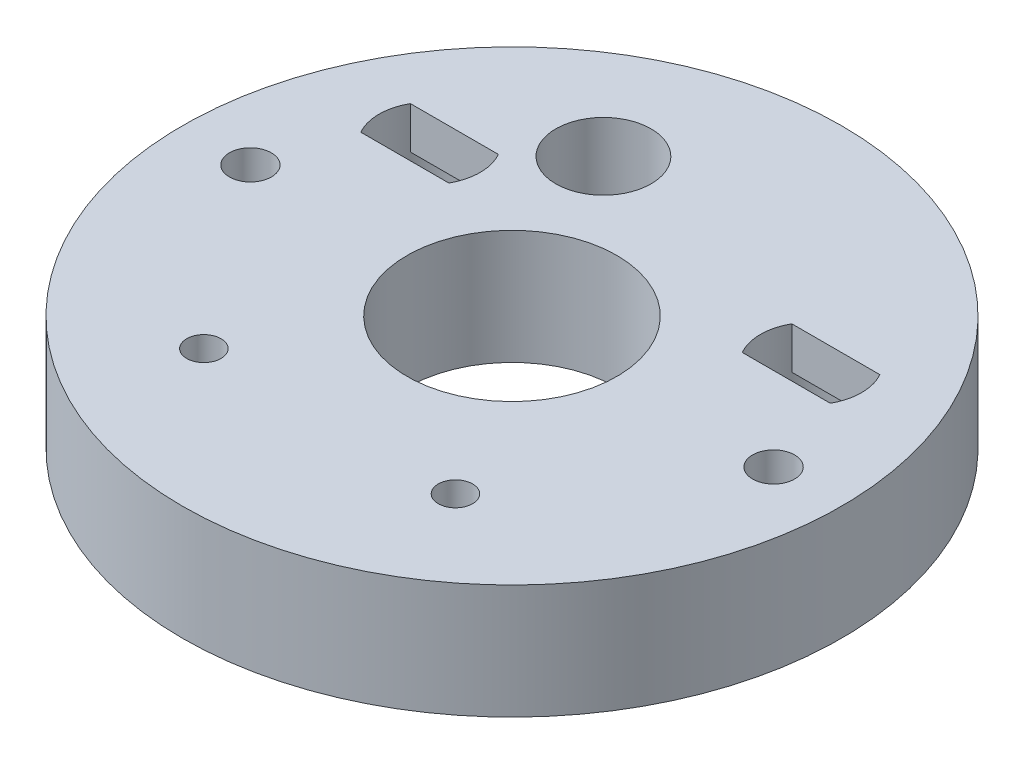
SolidWorks part; units mm, degrees
ref_plane "前视基准面" through (0, 0, 0) normal (0, 0, 1) x (1, 0, 0)
ref_plane "上视基准面" through (0, 0, 0) normal (0, 1, 0) x (1, 0, 0)
ref_plane "右视基准面" through (0, 0, 0) normal (1, 0, 0) x (0, 0, -1)
sketch "草图1" plane through (0, 0, 0) normal (0, 1, 0) x (1, 0, 0)
  line L0 (10, 5.6789) -> (-10, 5.6789) construction
  line L1 (0, 0) -> (0, 21.4139) construction
  line L2 (-6.595, -9.5611) -> (6.595, -9.5611) construction
  line L3 (-0.6445, -0.366) -> (22.2352, 12.6272) construction
  line L4 (0, 0) -> (2.6547, 0) construction
  circle A0 centre (0, 0) radius 17.28
  circle A1 centre (0, 0) radius 5 construction
  circle A2 centre (0, 0) radius 5.5
  circle A3 centre (10, 5.6789) radius 2.5 construction
  circle A4 centre (-10, 5.6789) radius 2.5 construction
  circle A5 centre (6.595, -9.5611) radius 1.76 construction
  circle A6 centre (-6.595, -9.5611) radius 1.76 construction
  circle A7 centre (-10, 5.6789) radius 2.65
  circle A8 centre (-6.595, -9.5611) radius 1.9
  circle A9 centre (6.595, -9.5611) radius 1.9
  circle A10 centre (10, 5.6789) radius 2.65
  point P14 (0, 5.6789)
  point P21 (0, -9.5611)
  point P24 (0, 0)
  dimension "D1" = 34.56
  dimension "D2" = 10
  dimension "D3" = 11
  dimension "D5" = 11.5
  dimension "D7" = 5
  dimension "D8" = 13.19
  dimension "D4" = 20
  dimension "D6" = 3.52
  dimension "D10" = 5.3
  dimension "D11" = 3.8
  dimension "D12" = 10
  dimension "D9" = 15.24
  dimension "D13" = 5.6789
  dimension "D14" = 9.5611
  dimension "D15" = 6.595
extrude "凸台-拉伸1" add sketch "草图1" along normal blind 3.8
sketch "草图2" plane through (0, 3.8, 0) normal (0, 1, 0) x (1, 0, 0)
  line L0 (-7.35, 18.1851) -> (-7.35, -3.106) construction
  line L1 (0, -200000) -> (0, 200021.4139) construction
  line L2 (0, 0) -> (-3.9187, 0) construction
  circle A1 centre (0, 0) radius 17.28
  circle A2 centre (0, 0) radius 17.28 construction
  circle A3 centre (-10, 5.6789) radius 2.5 construction
  circle A4 centre (-4.85, 9.6447) radius 2.5
  circle A6 centre (-10, 5.6789) radius 2.65 construction
  dimension "D2" = 6.5
  dimension "D3" = 5
  dimension "D4" = 4.85
  dimension "D5" = 9.6447
  dimension "D1" = 0
extrude "切除-拉伸1" cut sketch "草图2" against normal through all
sketch "草图3" plane through (0, 3.8, 0) normal (0, 1, 0) x (1, 0, 0)
  line L0 (-12.3092, 4.3789) -> (-7.6908, 4.3789)
  line L1 (-12.3092, 6.9789) -> (-7.6908, 6.9789)
  line L2 (-10, 6.9789) -> (-10, 4.3789) construction
  line L3 (0, 0) -> (0, 3.4524) construction
  line L4 (12.3092, 4.3789) -> (7.6908, 4.3789)
  line L5 (12.3092, 6.9789) -> (7.6908, 6.9789)
  circle A0 centre (6.595, -9.5611) radius 1.9 construction
  circle A1 centre (0, 0) radius 17.28
  circle A2 centre (0, 0) radius 17.28
  circle A3 centre (-6.595, -9.5611) radius 1.9 construction
  circle A5 centre (-10, 5.6789) radius 2.65 construction
  circle A6 centre (0, 0) radius 5.5 construction
  circle A7 centre (-4.85, 9.6447) radius 2.5 construction
  circle A8 centre (6.595, -9.5611) radius 1.9 construction
  circle A9 centre (-6.595, -9.5611) radius 1.9 construction
  arc A11 (-12.3092, 6.9789) -> (-12.3092, 4.3789) centre (-10, 5.6789) ccw
  circle A12 centre (0, 0) radius 5.5
  circle A13 centre (-4.85, 9.6447) radius 2.5
  arc A14 (-7.6908, 4.3789) -> (-7.6908, 6.9789) centre (-10, 5.6789) ccw
  arc A15 (7.6908, 4.3789) -> (7.6908, 6.9789) centre (10, 5.6789) cw
  arc A16 (12.3092, 6.9789) -> (12.3092, 4.3789) centre (10, 5.6789) cw
  circle A17 centre (-6.595, -9.5611) radius 0.9
  circle A18 centre (6.595, -9.5611) radius 0.9
  dimension "D3" = 1.8
  dimension "D2" = 2.6
  dimension "D1" = 0
extrude "凸台-拉伸2" add sketch "草图3" along normal blind 2.2
sketch "草图4" plane through (0, 6, 0) normal (0, 1, 0) x (1, 0, 0)
  line L0 (0, 0) -> (-31.0846, 0) construction
  circle A0 centre (-13.717, 0) radius 1.1
  circle A1 centre (13.717, 0) radius 1.1
  dimension "D1" = 13.717
  dimension "D3" = 2.2
  dimension "D4" = 2.2
  dimension "D2" = 13.717
extrude "切除-拉伸2" cut sketch "草图4" against normal through all
sketch "草图5" plane through (0, 0, 0) normal (0, -1, 0) x (1, 0, 0)
  line L0 (0, 0) -> (27.0843, 0) construction
  circle A0 centre (13.717, 0) radius 1.6
  circle A1 centre (-13.717, 0) radius 1.6
  dimension "D1" = 3.2
  dimension "D2" = 3.2
extrude "切除-拉伸3" cut sketch "草图5" against normal blind 3
